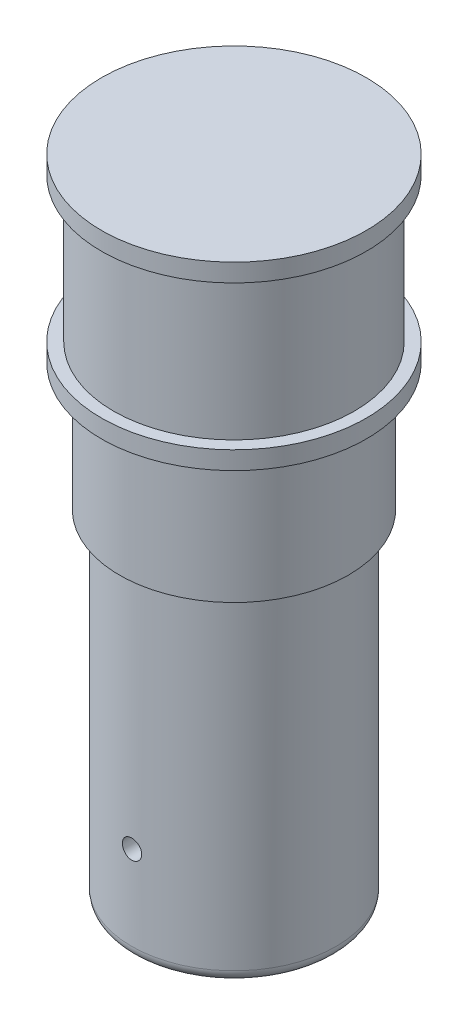
SolidWorks part; units mm, degrees
material "ABS"
ref_plane "Front Plane" through (0, 0, 0) normal (0, 0, 1) x (1, 0, 0)
ref_plane "Top Plane" through (0, 0, 0) normal (0, 1, 0) x (1, 0, 0)
ref_plane "Right Plane" through (0, 0, 0) normal (1, 0, 0) x (0, 0, -1)
sketch "Sketch1" plane through (0, 0, 0) normal (0, 0, 1) x (1, 0, 0)
  line L2 (-8.5, -38.75) -> (-8.5, -10.55)
  line L3 (-9.5, 0) -> (-11, 0)
  line L4 (-11, 0) -> (-11, 1.5)
  line L5 (-11, 1.5) -> (-10, 1.5)
  line L6 (-10, 1.5) -> (-10, 13.5)
  line L7 (-10, 13.5) -> (-11, 13.5)
  line L8 (-11, 13.5) -> (-11, 15)
  line L9 (-11, 15) -> (0, 15)
  line L10 (0, 15) -> (0, -24.75)
  line L11 (-4, -38.75) -> (-8.5, -38.75)
  line L12 (-4, -24.75) -> (-4, -38.75)
  line L13 (0, -24.75) -> (-4, -24.75)
  line L14 (-8.5, -10.55) -> (-9.5, -10.55)
  line L15 (-9.5, -10.55) -> (-9.5, 0)
  dimension "D1" = 8.5
  dimension "D2" = 1
  dimension "D3" = 38.75
  dimension "D4" = 1.5
  dimension "D5" = 4
  dimension "D6" = 14
  dimension "D7" = 15
  dimension "D8" = 10
  dimension "D9" = 28.2
  dimension "D10" = 1
revolve "Revolve1" add sketch "Sketch1" angle 360 about L10
fillet "Fillet1" radius 1 2 edges at (-8.5, -38.75, 0) (-4, -38.75, 0)
hole_wizard "M2x0.4 Tapped Hole1" positions "Sketch2" profile "Sketch3" tap size "M2x0.4" standard "ANSI Metric" end condition up to next
sketch "Sketch2" plane through (0, 0, 0) normal (0, 0, 1) x (1, 0, 0)
  line L0 (-7.5, -38.75) -> (7.5, -38.75) construction
  point P0 (0, -30.75)
  dimension "D1" = 8
sketch "Sketch3" plane through (0, -30.75, 0) normal (1, 0, 0) x (0, 1, 0)
  line L0 (0, 0) -> (0, 8.5)
  line L1 (0, 8.5) -> (0.8, 8.5)
  line L2 (0.8, 8.5) -> (0.8, 0)
  line L5 (0.8, 0) -> (0, 0)
  line L11 (0, -6.35) -> (0, 107.95) construction
  dimension "Thru Tap Drill Dia." = 1.6
  dimension "Thru Tap Drill Depth" = 8.5
cosmetic thread "Hole Thread1"
